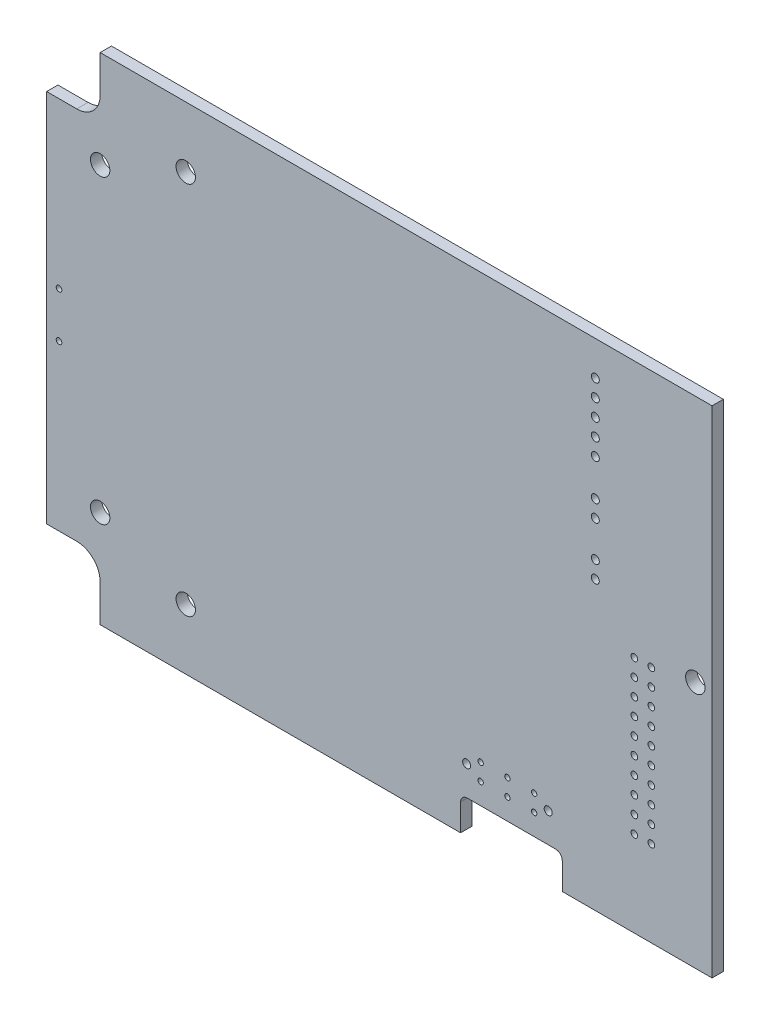
SolidWorks part; units mm, degrees
ref_plane "Płaszczyzna przednia" through (0, 0, 0) normal (0, 0, 1) x (1, 0, 0)
ref_plane "Płaszczyzna górna" through (0, 0, 0) normal (0, 1, 0) x (1, 0, 0)
ref_plane "Płaszczyzna prawa" through (0, 0, 0) normal (1, 0, 0) x (0, 0, -1)
ref_plane "Plane1" through (0, 0, 1.6894) normal (0, 0, 1) x (1, 0, 0)
sketch "Sketch1" plane through (0, 0, 1.6894) normal (0, 0, 1) x (1, 0, 0)
  line L0 (87.3, 25.4) -> (87.3, 29.4)
  line L8 (88.3, 30.4) -> (101.5, 30.4)
  line L16 (102.5, 29.4) -> (102.5, 25.4)
  line L17 (102.5, 25.4) -> (124.9, 25.4)
  line L18 (124.9, 25.4) -> (124.9, 99.5)
  line L19 (124.9, 99.5) -> (33.4, 99.5)
  line L20 (33.4, 99.5) -> (33.4, 93.95)
  line L30 (29.9, 90.45) -> (25.4, 90.45)
  line L31 (25.4, 90.45) -> (25.4, 34.45)
  line L32 (25.4, 34.45) -> (29.9, 34.45)
  line L42 (33.4, 30.95) -> (33.4, 25.4)
  line L43 (33.4, 25.4) -> (87.3, 25.4)
  arc A0 (29.9, 90.45) -> (33.4, 93.95) centre (29.9, 93.95) ccw
  arc A1 (29.9, 34.45) -> (33.4, 30.95) centre (29.9, 30.95) cw
  arc A2 (87.3, 29.4) -> (88.3, 30.4) centre (88.3, 29.4) cw
  arc A3 (101.5, 30.4) -> (102.5, 29.4) centre (101.5, 29.4) cw
extrude "Boss-Extrude1" add sketch "Sketch1" against normal blind 1.6894
hole_wizard "Ø2.9 (2.9) Diameter Hole1" positions "Sketch3" profile "Sketch2" hole size "Ø2.9" standard "ANSI Metric"
sketch "Sketch3" plane through (0, 0, 0) normal (0, 0, -1) x (-1, 0, 0)
  point P0 (-122.4, 62.45)
sketch "Sketch2" plane through (122.4, 62.45, 0) normal (1, 0, 0) x (0, 1, 0)
  line L0 (0, 0) -> (0, 1.6894)
  line L1 (0, 1.6894) -> (1.45, 1.6894)
  line L2 (1.45, 1.6894) -> (1.45, 0)
  line L5 (1.45, 0) -> (0, 0)
  line L11 (0, -6.35) -> (0, 107.95) construction
  dimension "Thru Hole Dia." = 2.9
  dimension "Thru Hole Depth" = 1.6894
hole_wizard "Hole1" positions "Sketch5" profile "Sketch4" legacy
sketch "Sketch5" plane through (0, 0, 0) normal (0, 0, -1) x (-1, 0, 0)
  point P0 (-107.4445, 78.74)
sketch "Sketch4" plane through (107.4445, 78.74, 0) normal (1, 0, 0) x (0, 1, 0)
  line L0 (0, 0) -> (0, 1.6894)
  line L1 (0, 1.6894) -> (0.6, 1.6894)
  line L2 (0.6, 1.6894) -> (0.6, 0)
  line L3 (0.6, 0) -> (0, 0)
  line L4 (0, 110) -> (0, -10) construction
  dimension "Diameter" = 1.2
  dimension "Depth" = 1.6894
sketch3d "3DSketch1"
  point P0 (75.7872, 62.8127, 0.8447)
  point P1 (75.5904, -37.1871, 0.8447)
ref_axis "Axis1" through (75.7872, 62.8127, 0.8447) along (-0.002, -1, 0)
pattern_linear "LPattern1" count 2 spacing 2.54 along (-0.002, -1, 0) of "Hole1"
hole_wizard "Hole2" positions "Sketch7" profile "Sketch6" legacy
sketch "Sketch7" plane through (0, 0, 0) normal (0, 0, -1) x (-1, 0, 0)
  point P0 (-113.284, 38.227)
sketch "Sketch6" plane through (113.284, 38.227, 0) normal (1, 0, 0) x (0, 1, 0)
  line L0 (0, 0) -> (0, 1.6894)
  line L1 (0, 1.6894) -> (0.5, 1.6894)
  line L2 (0.5, 1.6894) -> (0.5, 0)
  line L3 (0.5, 0) -> (0, 0)
  line L4 (0, 110) -> (0, -10) construction
  dimension "Diameter" = 1
  dimension "Depth" = 1.6894
sketch3d "3DSketch2"
  point P0 (175.778, 62.8132, 0.8447)
  point P1 (75.778, 62.8132, 0.8447)
ref_axis "Axis2" through (175.778, 62.8132, 0.8447) along (-1, 0, 0)
sketch3d "3DSketch3"
  point P0 (75.778, 162.8132, 0.8447)
  point P1 (75.778, 62.8132, 0.8447)
ref_axis "Axis3" through (75.778, 162.8132, 0.8447) along (0, -1, 0)
pattern_linear "LPattern2" count 2 spacing 2.54 along (1, 0, 0) count 10 spacing 2.54 along (0, 1, 0) of "Hole2"
hole_wizard "Hole3" positions "Sketch9" profile "Sketch8" legacy
sketch "Sketch9" plane through (0, 0, 0) normal (0, 0, -1) x (-1, 0, 0)
  point P0 (-107.442, 94.361)
sketch "Sketch8" plane through (107.442, 94.361, 0) normal (1, 0, 0) x (0, 1, 0)
  line L0 (0, 0) -> (0, 1.6894)
  line L1 (0, 1.6894) -> (0.6, 1.6894)
  line L2 (0.6, 1.6894) -> (0.6, 0)
  line L3 (0.6, 0) -> (0, 0)
  line L4 (0, 110) -> (0, -10) construction
  dimension "Diameter" = 1.2
  dimension "Depth" = 1.6894
sketch3d "3DSketch4"
  point P0 (75.6918, 62.8345, 0.8447)
  point P1 (75.6918, -37.1655, 0.8447)
ref_axis "Axis4" through (75.6918, 62.8345, 0.8447) along (0, -1, 0)
pattern_linear "LPattern3" count 5 spacing 2.54 along (0, -1, 0) of "Hole3"
hole_wizard "Ø2.9 (2.9) Diameter Hole2" positions "Sketch11" profile "Sketch10" hole size "Ø2.9" standard "ANSI Metric"
sketch "Sketch11" plane through (0, 0, 0) normal (0, 0, -1) x (-1, 0, 0)
  point P0 (-33.4, 84.95)
sketch "Sketch10" plane through (33.4, 84.95, 0) normal (1, 0, 0) x (0, 1, 0)
  line L0 (0, 0) -> (0, 1.6894)
  line L1 (0, 1.6894) -> (1.45, 1.6894)
  line L2 (1.45, 1.6894) -> (1.45, 0)
  line L5 (1.45, 0) -> (0, 0)
  line L11 (0, -6.35) -> (0, 107.95) construction
  dimension "Thru Hole Dia." = 2.9
  dimension "Thru Hole Depth" = 1.6894
hole_wizard "Hole4" positions "Sketch13" profile "Sketch12" legacy
sketch "Sketch13" plane through (0, 0, 0) normal (0, 0, -1) x (-1, 0, 0)
  point P0 (-107.4395, 68.326)
sketch "Sketch12" plane through (107.4395, 68.326, 0) normal (1, 0, 0) x (0, 1, 0)
  line L0 (0, 0) -> (0, 1.6894)
  line L1 (0, 1.6894) -> (0.6, 1.6894)
  line L2 (0.6, 1.6894) -> (0.6, 0)
  line L3 (0.6, 0) -> (0, 0)
  line L4 (0, 110) -> (0, -10) construction
  dimension "Diameter" = 1.2
  dimension "Depth" = 1.6894
sketch3d "3DSketch5"
  point P0 (75.7058, 62.7971, 0.8447)
  point P1 (75.9026, 162.7969, 0.8447)
ref_axis "Axis5" through (75.7058, 62.7971, 0.8447) along (0.002, 1, 0)
pattern_linear "LPattern4" count 2 spacing 2.54 along (0.002, 1, 0) of "Hole4"
hole_wizard "Ø0.85 (0.85) Diameter Hole1" positions "Sketch15" profile "Sketch14" hole size "Ø0.85" standard "ANSI Metric"
sketch "Sketch15" plane through (0, 0, 0) normal (0, 0, -1) x (-1, 0, 0)
  point P0 (-27.2501, 65.85)
sketch "Sketch14" plane through (27.2501, 65.85, 0) normal (1, 0, 0) x (0, 1, 0)
  line L0 (0, 0) -> (0, 1.6894)
  line L1 (0, 1.6894) -> (0.425, 1.6894)
  line L2 (0.425, 1.6894) -> (0.425, 0)
  line L5 (0.425, 0) -> (0, 0)
  line L11 (0, -6.35) -> (0, 107.95) construction
  dimension "Thru Hole Dia." = 0.85
  dimension "Thru Hole Depth" = 1.6894
hole_wizard "Hole5" positions "Sketch17" profile "Sketch16" legacy
sketch "Sketch17" plane through (0, 0, 0) normal (0, 0, -1) x (-1, 0, 0)
  point P0 (-90.3, 36.05)
sketch "Sketch16" plane through (90.3, 36.05, 0) normal (1, 0, 0) x (0, 1, 0)
  line L0 (0, 0) -> (0, 1.6894)
  line L1 (0, 1.6894) -> (0.4, 1.6894)
  line L2 (0.4, 1.6894) -> (0.4, 0)
  line L3 (0.4, 0) -> (0, 0)
  line L4 (0, 110) -> (0, -10) construction
  dimension "Diameter" = 0.8
  dimension "Depth" = 1.6894
sketch3d "3DSketch6"
  point P0 (175.7036, 62.7975, 0.8447)
  point P1 (75.7036, 62.7975, 0.8447)
ref_axis "Axis6" through (175.7036, 62.7975, 0.8447) along (-1, 0, 0)
sketch3d "3DSketch7"
  point P0 (75.7036, -37.2025, 0.8447)
  point P1 (75.7036, 62.7975, 0.8447)
ref_axis "Axis7" through (75.7036, -37.2025, 0.8447) along (0, 1, 0)
pattern_linear "LPattern5" count 3 spacing 4 along (1, 0, 0) count 2 spacing 2.5 along (0, -1, 0) of "Hole5"
hole_wizard "Ø2.9 (2.9) Diameter Hole3" positions "Sketch19" profile "Sketch18" hole size "Ø2.9" standard "ANSI Metric"
sketch "Sketch19" plane through (0, 0, 0) normal (0, 0, -1) x (-1, 0, 0)
  point P0 (-33.4, 39.95)
sketch "Sketch18" plane through (33.4, 39.95, 0) normal (1, 0, 0) x (0, 1, 0)
  line L0 (0, 0) -> (0, 1.6894)
  line L1 (0, 1.6894) -> (1.45, 1.6894)
  line L2 (1.45, 1.6894) -> (1.45, 0)
  line L5 (1.45, 0) -> (0, 0)
  line L11 (0, -6.35) -> (0, 107.95) construction
  dimension "Thru Hole Dia." = 2.9
  dimension "Thru Hole Depth" = 1.6894
hole_wizard "Ø2.9 (2.9) Diameter Hole4" positions "Sketch21" profile "Sketch20" hole size "Ø2.9" standard "ANSI Metric"
sketch "Sketch21" plane through (0, 0, 0) normal (0, 0, -1) x (-1, 0, 0)
  point P0 (-46.2, 34.45)
sketch "Sketch20" plane through (46.2, 34.45, 0) normal (1, 0, 0) x (0, 1, 0)
  line L0 (0, 0) -> (0, 1.6894)
  line L1 (0, 1.6894) -> (1.45, 1.6894)
  line L2 (1.45, 1.6894) -> (1.45, 0)
  line L5 (1.45, 0) -> (0, 0)
  line L11 (0, -6.35) -> (0, 107.95) construction
  dimension "Thru Hole Dia." = 2.9
  dimension "Thru Hole Depth" = 1.6894
hole_wizard "Ø0.85 (0.85) Diameter Hole2" positions "Sketch23" profile "Sketch22" hole size "Ø0.85" standard "ANSI Metric"
sketch "Sketch23" plane through (0, 0, 0) normal (0, 0, -1) x (-1, 0, 0)
  point P0 (-27.2501, 59.05)
sketch "Sketch22" plane through (27.2501, 59.05, 0) normal (1, 0, 0) x (0, 1, 0)
  line L0 (0, 0) -> (0, 1.6894)
  line L1 (0, 1.6894) -> (0.425, 1.6894)
  line L2 (0.425, 1.6894) -> (0.425, 0)
  line L5 (0.425, 0) -> (0, 0)
  line L11 (0, -6.35) -> (0, 107.95) construction
  dimension "Thru Hole Dia." = 0.85
  dimension "Thru Hole Depth" = 1.6894
hole_wizard "Hole6" positions "Sketch25" profile "Sketch24" legacy
sketch "Sketch25" plane through (0, 0, 0) normal (0, 0, -1) x (-1, 0, 0)
  point P0 (-88.2, 34.8)
sketch "Sketch24" plane through (88.2, 34.8, 0) normal (1, 0, 0) x (0, 1, 0)
  line L0 (0, 0) -> (0, 1.6894)
  line L1 (0, 1.6894) -> (0.6, 1.6894)
  line L2 (0.6, 1.6894) -> (0.6, 0)
  line L3 (0.6, 0) -> (0, 0)
  line L4 (0, 110) -> (0, -10) construction
  dimension "Diameter" = 1.2
  dimension "Depth" = 1.6894
sketch3d "3DSketch8"
  point P0 (75.7654, 62.8599, 0.8447)
  point P1 (175.7654, 62.8599, 0.8447)
ref_axis "Axis8" through (75.7654, 62.8599, 0.8447) along (1, 0, 0)
pattern_linear "LPattern6" count 2 spacing 12.2 along (1, 0, 0) of "Hole6"
hole_wizard "Ø2.9 (2.9) Diameter Hole5" positions "Sketch27" profile "Sketch26" hole size "Ø2.9" standard "ANSI Metric"
sketch "Sketch27" plane through (0, 0, 0) normal (0, 0, -1) x (-1, 0, 0)
  point P0 (-46.2, 90.45)
sketch "Sketch26" plane through (46.2, 90.45, 0) normal (1, 0, 0) x (0, 1, 0)
  line L0 (0, 0) -> (0, 1.6894)
  line L1 (0, 1.6894) -> (1.45, 1.6894)
  line L2 (1.45, 1.6894) -> (1.45, 0)
  line L5 (1.45, 0) -> (0, 0)
  line L11 (0, -6.35) -> (0, 107.95) construction
  dimension "Thru Hole Dia." = 2.9
  dimension "Thru Hole Depth" = 1.6894
